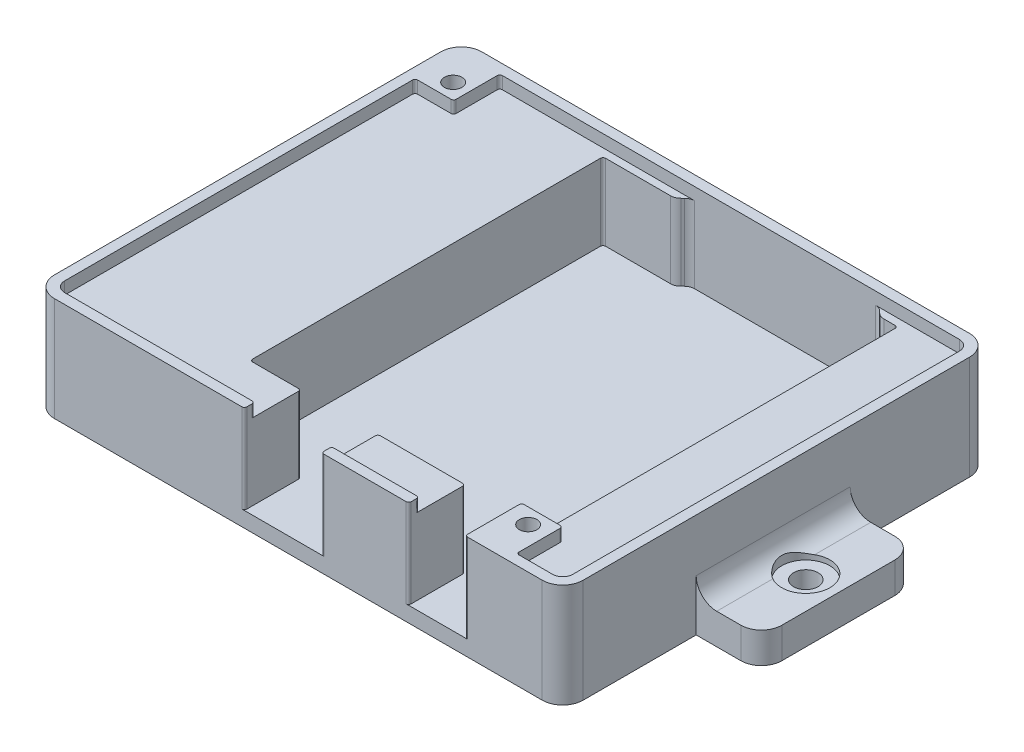
SolidWorks part; units mm, degrees
ref_plane "Front Plane" through (0, 0, 0) normal (0, 0, 1) x (1, 0, 0)
ref_plane "Top Plane" through (0, 0, 0) normal (0, 1, 0) x (1, 0, 0)
ref_plane "Right Plane" through (0, 0, 0) normal (1, 0, 0) x (0, 0, -1)
sketch "Sketch1" plane through (0, 0, 0) normal (0, 1, 0) x (1, 0, 0)
  line L1 (0, 0) -> (103, 0)
  line L2 (0, 0) -> (0, 83.25)
  line L3 (0, 83.25) -> (103, 83.25)
  line L4 (103, 0) -> (103, 83.25)
  dimension "D1" = 83.25
  dimension "D2" = 103
extrude "Boss-Extrude1" add sketch "Sketch1" along normal blind 20.2438
sketch "Sketch2" plane through (0, 20.2438, 0) normal (0, 1, 0) x (1, 0, 0)
  line L0 (0, 83.25) -> (0, 0) construction
  line L1 (31.1, 79.75) -> (45.1, 79.75)
  line L2 (31.1, 79.75) -> (31.1, 11)
  line L3 (31.1, 11) -> (88.5, 11)
  line L4 (88.5, 79.75) -> (88.5, 11)
  line L5 (103, 83.25) -> (0, 83.25) construction
  line L6 (85, 79.75) -> (88.5, 79.75)
  line L8 (45.85, 80.5) -> (45.85, 81.25) construction
  line L9 (46.6, 81.25) -> (83.5, 81.25)
  line L10 (84.25, 80.5) -> (84.25, 81.25) construction
  line L11 (103, 0) -> (103, 83.25) construction
  line L12 (45.1, 79.75) -> (46.6, 81.25)
  line L13 (85, 79.75) -> (83.5, 81.25)
  line L14 (84.25, 79.75) -> (84.25, 80.5) construction
  line L15 (84.25, 79.75) -> (85, 79.75) construction
  line L16 (83.5, 81.25) -> (84.25, 81.25) construction
  line L17 (45.1, 79.75) -> (45.85, 79.75) construction
  line L18 (45.85, 79.75) -> (45.85, 80.5) construction
  line L19 (45.85, 81.25) -> (46.6, 81.25) construction
  point P18 (84.25, 80.5)
  point P19 (45.85, 80.5)
  dimension "D1" = 31.1
  dimension "D2" = 3.5
  dimension "D3" = 2
  dimension "D4" = 14.75
  dimension "D5" = 4.25
  dimension "D6" = 68.75
  dimension "D7" = 14.5
  dimension "D8" = 38.4
  dimension "D9" = 45
  dimension "D10" = 45
extrude "Cut-Extrude1" cut sketch "Sketch2" against normal offset from surface (17.2438 mm away) 3 up to face at (51.5, 0, -41.625)
sketch "Sketch3" plane through (0, 0, 0) normal (0, 0, 1) x (1, 0, 0)
  line L0 (0, 20.2438) -> (103, 20.2438) construction
  line L1 (41, 20.2438) -> (56, 20.2438)
  line L2 (41, 20.2438) -> (41, 3)
  line L3 (41, 3) -> (56, 3)
  line L4 (56, 20.2438) -> (56, 3)
  line L5 (0, 20.2438) -> (0, 0) construction
  line L6 (73, 20.2438) -> (84, 20.2438)
  line L7 (73, 20.2438) -> (73, 3)
  line L8 (73, 3) -> (84, 3)
  line L9 (84, 20.2438) -> (84, 3)
  line L10 (31.1, 3) -> (88.5, 3) construction
  dimension "D1" = 17.2438
  dimension "D2" = 15
  dimension "D3" = 41
  dimension "D4" = 11
  dimension "D6" = 17
extrude "Cut-Extrude2" cut sketch "Sketch3" against normal blind 14.9225
sketch "Sketch4" plane through (0, 20.2438, 0) normal (0, 1, 0) x (1, 0, 0)
  line L0 (0, 83.25) -> (0, 0) construction
  line L1 (9.5, 81.25) -> (101, 81.25)
  line L2 (2, 72.25) -> (2, 2)
  line L3 (2, 2) -> (84, 2)
  line L4 (101, 81.25) -> (101, 2)
  line L5 (0, 0) -> (41, 0) construction
  line L6 (2, 72.25) -> (9.5, 72.25)
  line L7 (9.5, 72.25) -> (9.5, 81.25)
  line L8 (92, 2) -> (92, 11)
  line L9 (92, 11) -> (84, 11)
  line L10 (84, 11) -> (84, 2)
  line L11 (84, 11) -> (84, 0) construction
  line L12 (92, 2) -> (101, 2)
  line L13 (103, 0) -> (103, 83.25) construction
  line L14 (103, 83.25) -> (0, 83.25) construction
  dimension "D1" = 2
  dimension "D2" = 2
  dimension "D3" = 2
  dimension "D4" = 2
  dimension "D5" = 9.5
  dimension "D6" = 11
  dimension "D7" = 8
  dimension "D8" = 11
  dimension "D9" = 19
extrude "Cut-Extrude3" cut sketch "Sketch4" against normal blind 2.4
sketch "Sketch5" plane through (0, 0, 0) normal (-1, 0, 0) x (0, 0, 1)
  line L0 (-83.25, 0) -> (0, 0) construction
  line L1 (-56, 0) -> (-26, 0)
  line L2 (-56, 0) -> (-56, 6)
  line L3 (-56, 6) -> (-26, 6)
  line L4 (-26, 0) -> (-26, 6)
  line L6 (0, 20.2438) -> (0, 0) construction
  dimension "D1" = 30
  dimension "D2" = 26
  dimension "D3" = 6
extrude "Boss-Extrude2" add sketch "Sketch5" along normal blind 12.7
ref_plane "Plane1" through (51.5, 0, 0) normal (-1, 0, 0) x (0, 0, 1)
ref_plane "Plane2" through (0, 0, -41.625) normal (0, 0, 1) x (1, 0, 0)
mirror "Mirror1" about plane through (51.5, 0, 0) normal (-1, 0, 0) of "Boss-Extrude2"
sketch "Sketch6" plane through (0, 0, -83.25) normal (0, 0, -1) x (-1, 0, 0)
  line L0 (-103, 0) -> (0, 0) construction
  line L1 (-66.5, 0) -> (-36.5, 0)
  line L2 (-66.5, 0) -> (-66.5, 6)
  line L3 (-66.5, 6) -> (-36.5, 6)
  line L4 (-36.5, 0) -> (-36.5, 6)
  line L6 (-66.5, 0) -> (-36.5, 6) construction
  line L7 (-51.5, -11.1341) -> (-51.5, 11.1341) construction
  point P8 (-51.5, 3)
  dimension "D1" = 30
  dimension "D2" = 6
extrude "Boss-Extrude3" add sketch "Sketch6" along normal blind 12.7
fillet "Fillet1" radius 4 4 edges at (103, 10.1219, 0) (103, 10.1219, -83.25) (0, 10.1219, -83.25) (0, 10.1219, 0)
fillet "Fillet2" radius 0.5 20 edges at (41, 10.4219, -11) (56, 10.4219, -11) (73, 10.4219, -11) (92, 19.0438, -11) (84, 11.6219, -11) (9.5, 19.0438, -72.25) (84, 11.6219, 0) (56, 19.0438, -2) (41, 19.0438, -2) (73, 19.0438, -2) (73, 11.6219, 0) (56, 11.6219, 0) (41, 11.6219, 0) (92, 19.0438, -2) (9.5, 19.0438, -81.25) (2, 19.0438, -72.25) (88.5, 10.4219, -11) (31.1, 10.4219, -11) (31.1, 10.4219, -79.75) (88.5, 10.4219, -79.75)
fillet "Fillet3" radius 2 3 edges at (101, 19.0438, -81.25) (101, 19.0438, -2) (2, 19.0438, -2)
fillet "Fillet4" radius 4 9 edges at (0, 6, -41) (51.5, 6, -83.25) (103, 6, -41) (115.7, 3, -26) (115.7, 3, -56) (66.5, 3, -95.95) (36.5, 3, -95.95) (-12.7, 3, -56) (-12.7, 3, -26)
fillet "Fillet5" radius 2 4 edges at (45.1, 10.4219, -79.75) (46.6, 10.4219, -81.25) (85, 10.4219, -79.75) (83.5, 10.4219, -81.25)
sketch "Sketch7" plane through (0, 20.2438, 0) normal (0, 1, 0) x (1, 0, 0)
  line L1 (88.265, 8.0025) -> (6.35, 8.0025) construction
  line L2 (88.265, 8.0025) -> (88.265, 75.3125) construction
  line L3 (88.265, 75.3125) -> (6.35, 75.3125) construction
  line L4 (6.35, 8.0025) -> (6.35, 75.3125) construction
  line L5 (88.265, 8.0025) -> (6.35, 75.3125) construction
  line L6 (88.265, 75.3125) -> (6.35, 8.0025) construction
  line L8 (99, 83.25) -> (4, 83.25) construction
  line L9 (0, 79.25) -> (0, 4) construction
  line L10 (84.5, 11) -> (91.5, 11) construction
  line L12 (103, 4) -> (103, 79.25) construction
  circle A0 centre (6.35, 75.3125) radius 1.7145
  circle A1 centre (88.265, 8.0025) radius 1.7145
  point P4 (47.3075, 41.6575)
  dimension "D1" = 3.429
  dimension "D2" = 7.9375
  dimension "D3" = 6.35
  dimension "D4" = 2.9975
  dimension "D5" = 14.735
  dimension "D6" = 67.31
  dimension "D7" = 81.915
extrude "Cut-Extrude4" cut sketch "Sketch7" against normal through all
sketch "Sketch8" plane through (0, 0, 0) normal (0, -1, 0) x (1, 0, 0)
  circle A0 centre (6.35, -75.3125) radius 3.81
  circle A1 centre (88.265, -8.0025) radius 3.81
  dimension "D1" = 7.62
extrude "Cut-Extrude5" cut sketch "Sketch8" against normal blind 3.302
sketch "Sketch11" plane through (0, 6, 0) normal (0, 1, 0) x (1, 0, 0)
  line L0 (-6.35, 56) -> (-6.35, 26) construction
  line L1 (-8.7, 56) -> (-4, 56) construction
  line L2 (-8.7, 26) -> (-4, 26) construction
  line L3 (36.5, 89.6) -> (66.5, 89.6) construction
  line L4 (36.5, 91.95) -> (36.5, 87.25) construction
  line L5 (66.5, 91.95) -> (66.5, 87.25) construction
  line L6 (-12.7, 30) -> (-12.7, 52) construction
  line L7 (-6.35, 41) -> (-12.7, 41) construction
  line L8 (51.5, 89.6) -> (51.5, 95.95) construction
  line L9 (109.35, 41) -> (115.7, 41) construction
  line L10 (115.7, 30) -> (115.7, 52) construction
  line L11 (40.5, 95.95) -> (62.5, 95.95) construction
  circle A0 centre (-6.35, 41) radius 2.3812
  circle A1 centre (51.5, 89.6) radius 2.3812
  circle A2 centre (109.35, 41) radius 2.3813
  point P12 (51.5, 89.6)
  point P13 (-6.35, 41)
  point P28 (51.5, 89.6)
  point P31 (109.35, 41)
  point P32 (-6.35, 41)
  dimension "D1" = 4.7625
  dimension "D2" = 6.35
extrude "Cut-Extrude7" cut sketch "Sketch11" against normal through all contours A0
sketch "Sketch12" plane through (0, 6, 0) normal (0, 1, 0) x (1, 0, 0)
  circle A0 centre (-6.35, 41) radius 4.699
  dimension "D1" = 9.398
extrude "Cut-Extrude8" cut sketch "Sketch12" against normal blind 1 and the other way through all
pattern_sketch "Sketch-Pattern2" of "Cut-Extrude7", "Cut-Extrude8" driven by "Sketch11"
